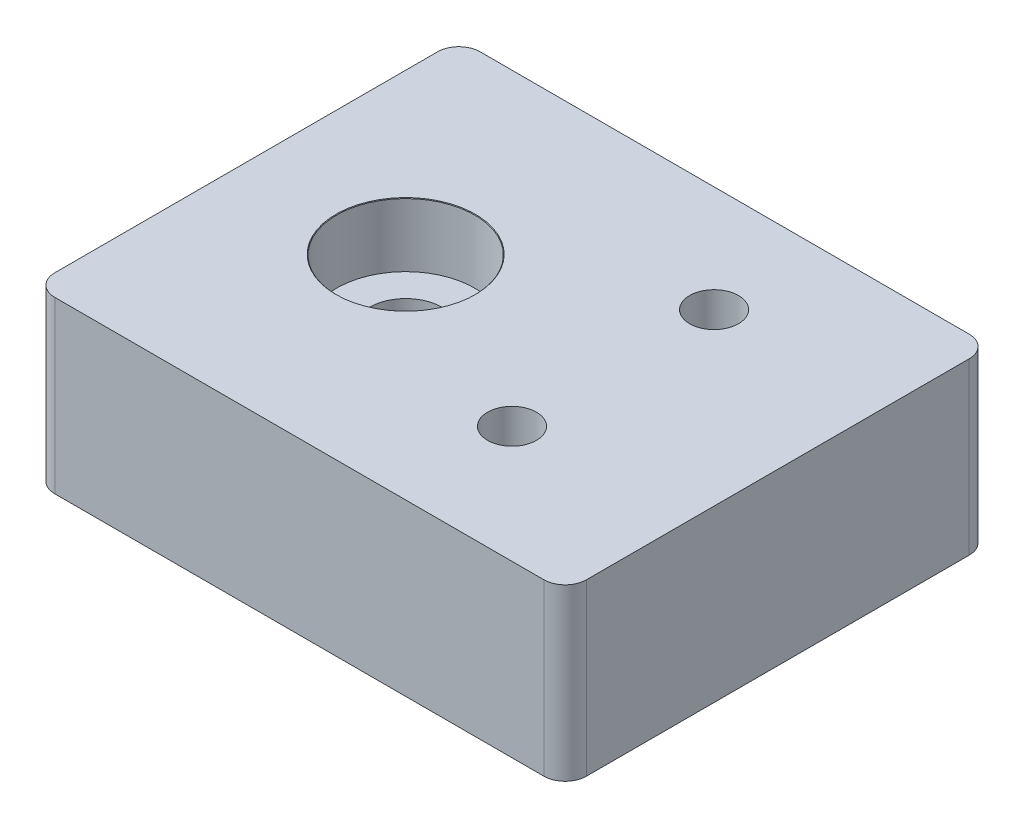
SolidWorks part; units mm, degrees
ref_plane "Front Plane" through (0, 0, 0) normal (0, 0, 1) x (1, 0, 0)
ref_plane "Top Plane" through (0, 0, 0) normal (0, 1, 0) x (1, 0, 0)
ref_plane "Right Plane" through (0, 0, 0) normal (1, 0, 0) x (0, 0, -1)
sketch "Sketch1" plane through (0, 0, 0) normal (0, 1, 0) x (1, 0, 0)
  line L1 (12.5, 10) -> (-12.5, 10)
  line L2 (12.5, 10) -> (12.5, -10)
  line L3 (12.5, -10) -> (-12.5, -10)
  line L4 (-12.5, 10) -> (-12.5, -10)
  line L5 (12.5, 10) -> (-12.5, -10) construction
  line L6 (12.5, -10) -> (-12.5, 10) construction
  point P0 (0, 0)
  dimension "D1" = 20
  dimension "D2" = 25
extrude "Boss-Extrude1" add sketch "Sketch1" along normal blind 8
sketch "Sketch2" plane through (0, 8, 0) normal (0, 1, 0) x (1, 0, 0)
  line L0 (12.5, 10) -> (-12.5, 10) construction
  line L1 (-12.5, 10) -> (-12.5, -10) construction
  point P0 (-5, 0)
  dimension "D1" = 10
  dimension "D2" = 7.5
hole_wizard "CBORE for M3 SHCS1" positions "Sketch3" profile "Sketch4" counterbore size "M3" standard "ANSI Metric" end condition through all
sketch "Sketch3" plane through (0, 8, 0) normal (0, 1, 0) x (1, 0, 0)
  point P4 (-5, 0)
sketch "Sketch4" plane through (-5, 8, 0) normal (1, 0, 0) x (0, 0, 1)
  line L0 (0, 0) -> (0, 8)
  line L1 (0, 8) -> (1.7, 8)
  line L3 (1.7, 8) -> (1.7, 3)
  line L4 (3.25, 3) -> (1.7, 3)
  line L5 (3.25, 3) -> (3.25, 0.025)
  line L6 (3.25, 0.025) -> (3.275, 0)
  line L7 (3.275, 0) -> (0, 0)
  line L8 (-3.25, 0.025) -> (-3.275, 0) construction
  line L11 (0, -6.35) -> (0, 107.95) construction
  dimension "Thru Hole Dia." = 3.4
  dimension "Thru Hole Depth" = 8
  dimension "C'Bore Dia." = 6.5
  dimension "C'Bore Depth" = 3
  dimension "Near C'Sink Dia." = 6.55
  dimension "Near C'Sink Angle" = 90
fillet "Fillet1" radius 1 4 edges at (12.5, 4, 10) (-12.5, 4, 10) (12.5, 4, -10) (-12.5, 4, -10)
sketch "Sketch5" plane through (0, 8, 0) normal (0, 1, 0) x (1, 0, 0)
  line L0 (-11.5, -10) -> (11.5, -10) construction
  line L1 (11.5, 10) -> (-11.5, 10) construction
  line L2 (12.5, -9) -> (12.5, 9) construction
  line L3 (4.5, 5) -> (4.5, -4.5) construction
  circle A0 centre (4.5, 5) radius 1.15
  circle A1 centre (4.5, -4.5) radius 1.15
  dimension "D1" = 5.5
  dimension "D2" = 5
  dimension "D3" = 2.3
  dimension "D4" = 8
extrude "Cut-Extrude1" cut sketch "Sketch5" against normal blind 5
